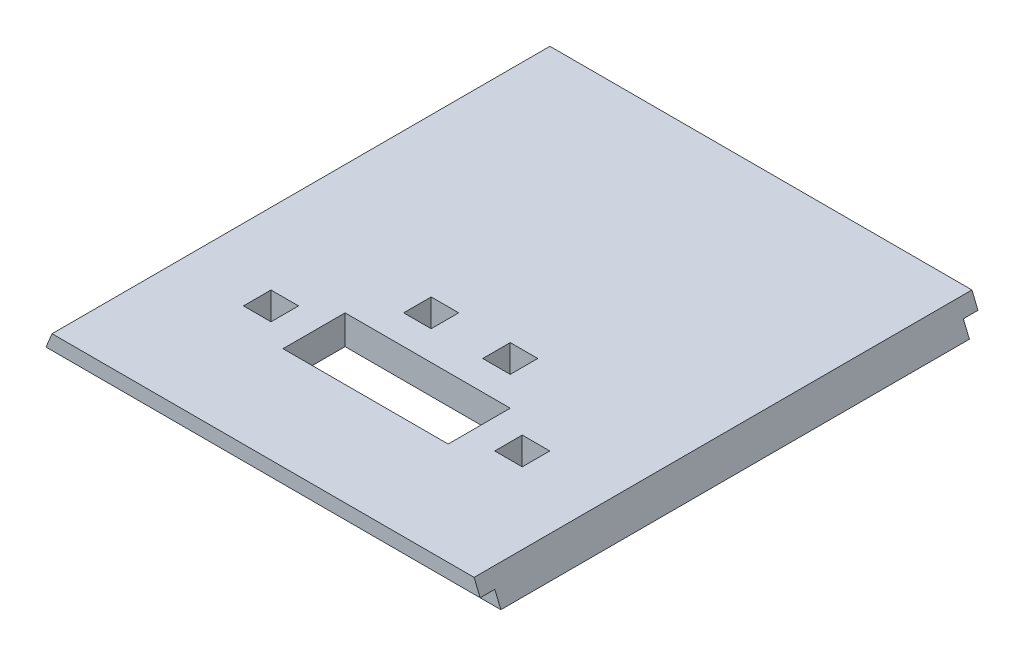
SolidWorks part; units mm, degrees
ref_plane "Front Plane" through (0, 0, 0) normal (0, 0, 1) x (1, 0, 0)
ref_plane "Top Plane" through (0, 0, 0) normal (0, 1, 0) x (1, 0, 0)
ref_plane "Right Plane" through (0, 0, 0) normal (1, 0, 0) x (0, 0, -1)
sketch "Sketch1" plane through (0, 0, 0) normal (0, 0, 1) x (1, 0, 0)
  line L0 (0, 0) -> (5.2605, 12.7)
  line L1 (5.2605, 12.7) -> (188.2875, 12.7)
  line L2 (188.2875, 12.7) -> (193.548, 0)
  line L3 (193.548, 0) -> (0, 0)
  dimension "D1" = 67.5
  dimension "D2" = 67.5
  dimension "D3" = 12.7
  dimension "D4" = 193.548
extrude "Boss-Extrude1" add sketch "Sketch1" along normal blind 215.9
sketch "Sketch2" plane through (0, 0, 0) normal (0, -1, 0) x (1, 0, 0)
  line L0 (0, 215.9) -> (0, 0) construction
  line L1 (0, 6.35) -> (193.548, 6.35)
  line L2 (0, 6.35) -> (0, 0)
  line L3 (0, 0) -> (193.548, 0)
  line L4 (193.548, 6.35) -> (193.548, 0)
  line L10 (193.548, 215.9) -> (193.548, 0) construction
  line L11 (0, 215.9) -> (193.548, 215.9)
  line L12 (0, 215.9) -> (0, 209.55)
  line L13 (0, 209.55) -> (193.548, 209.55)
  line L14 (193.548, 215.9) -> (193.548, 209.55)
  dimension "D1" = 6.35
  dimension "D2" = 6.35
extrude "Cut-Extrude1" cut sketch "Sketch2" against normal blind 6.35
sketch "Sketch3" plane through (0, 0, 0) normal (0, -1, 0) x (1, 0, 0)
  line L1 (60.96, 171.45) -> (132.588, 171.45)
  line L2 (60.96, 171.45) -> (60.96, 144.526)
  line L3 (60.96, 144.526) -> (132.588, 144.526)
  line L4 (132.588, 171.45) -> (132.588, 144.526)
  line L5 (0, 209.55) -> (0, 6.35) construction
  line L6 (0, 215.9) -> (193.548, 215.9) construction
  line L7 (73.66, 131.826) -> (85.598, 131.826)
  line L8 (73.66, 131.826) -> (73.66, 119.888)
  line L9 (73.66, 119.888) -> (85.598, 119.888)
  line L10 (85.598, 131.826) -> (85.598, 119.888)
  line L11 (107.95, 131.826) -> (119.888, 131.826)
  line L12 (107.95, 131.826) -> (107.95, 119.888)
  line L13 (107.95, 119.888) -> (119.888, 119.888)
  line L14 (119.888, 131.826) -> (119.888, 119.888)
  line L15 (145.288, 163.957) -> (157.226, 163.957)
  line L16 (145.288, 163.957) -> (145.288, 152.019)
  line L17 (145.288, 152.019) -> (157.226, 152.019)
  line L18 (157.226, 163.957) -> (157.226, 152.019)
  line L19 (36.322, 163.957) -> (48.26, 163.957)
  line L20 (36.322, 163.957) -> (36.322, 152.019)
  line L21 (36.322, 152.019) -> (48.26, 152.019)
  line L22 (48.26, 163.957) -> (48.26, 152.019)
  point P24 (48.26, 157.988)
  point P25 (60.96, 157.988)
  dimension "D1" = 71.628
  dimension "D2" = 26.924
  dimension "D3" = 44.45
  dimension "D4" = 60.96
  dimension "D5" = 11.938
  dimension "D6" = 12.7
  dimension "D7" = 12.7
  dimension "D8" = 12.7
  dimension "D9" = 12.7
  dimension "D10" = 12.7
extrude "Cut-Extrude3" cut sketch "Sketch3" against normal through all
